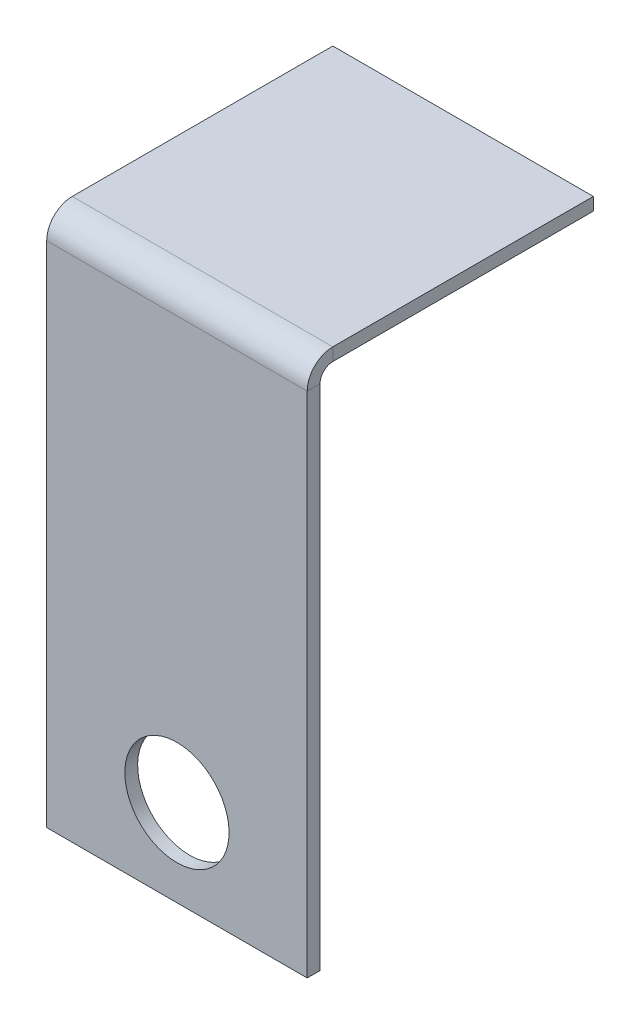
SolidWorks part; units mm, degrees
note: The reader was unsure of these and kept them because the rebuilt part matched: flange length of "Edge-Flange1".
ref_plane "Front Plane" through (0, 0, 0) normal (0, 0, 1) x (1, 0, 0)
ref_plane "Top Plane" through (0, 0, 0) normal (0, 1, 0) x (1, 0, 0)
ref_plane "Right Plane" through (0, 0, 0) normal (1, 0, 0) x (0, 0, -1)
sketch "Sketch1" plane through (0, 0, 0) normal (0, 1, 0) x (1, 0, 0)
  line L1 (-7.5, 7.5) -> (7.5, 7.5)
  line L2 (-7.5, 7.5) -> (-7.5, -7.5)
  line L3 (-7.5, -7.5) -> (7.5, -7.5)
  line L4 (7.5, 7.5) -> (7.5, -7.5)
  line L5 (-7.5, 7.5) -> (7.5, -7.5) construction
  line L6 (-7.5, -7.5) -> (7.5, 7.5) construction
  point P0 (0, 0)
  dimension "D1" = 15
  dimension "D2" = 15
base flange "Base-Flange1" sketch "Sketch1" thickness 0.7366 reverse thickness direction no parameters "D1"=0.7366
edge flange "Edge-Flange1" sketch "Sketch8" flange angle 90 flange length 30 flange position bend outside bend radius 0.7366 thickness 0.7366 relief rectangular parameters "D6"=10
sketch "Sketch8" plane through (0, -0.7366, 7.5) normal (0, 0, -1) x (1, 0, 0)
  line L1 (7.5, 0) -> (-7.5, 0) construction
  line L2 (-7.5, 0) -> (-7.5, 30)
  line L3 (-7.5, 30) -> (7.5, 30)
  line L4 (7.5, 30) -> (7.5, 0)
  line L5 (7.5, 0) -> (-7.5, 0)
  line L6 (0, 0) -> (0, 32.9407) construction
  circle A0 centre (0, 25) radius 3
  dimension "D1" = 6
  dimension "D2" = 25
  dimension "D3" = 5
bend "EdgeBend1" bend radius 0.7366 bend angle 90 parameters "D5"=1
sketch "Bend-Lines1" plane through (0, 0, 0) normal (0, 1, 0) x (1, 0, 0)
sketch "Bounding-Box1" plane through (0, 0, 0) normal (0, 1, 0) x (1, 0, 0)
sheet metal parameters "Sheet-Metal(1)" thickness 0.7366 parameters "D1"=0.7366
flat pattern "Flat-Pattern(1)" [suppressed]
sketch "Bend-Lines2" plane through (0, 0, 0) normal (0, 1, 0) x (1, 0, 0)
sketch "Bounding-Box2" [suppressed] plane through (0, 0, 0) normal (0, 1, 0) x (1, 0, 0)
sheet metal parameters "Sheet-Metal(2)" thickness 0.7366 parameters "D1"=0.7366
flat pattern "Flat-Pattern(1)" [suppressed]
sketch "Bend-Lines3" plane through (0, 0, 0) normal (0, 1, 0) x (1, 0, 0)
sketch "Bounding-Box3" [suppressed] plane through (0, 0, 0) normal (0, 1, 0) x (1, 0, 0)
bend of the flat pattern "Flatten-<EdgeBend1>1"
